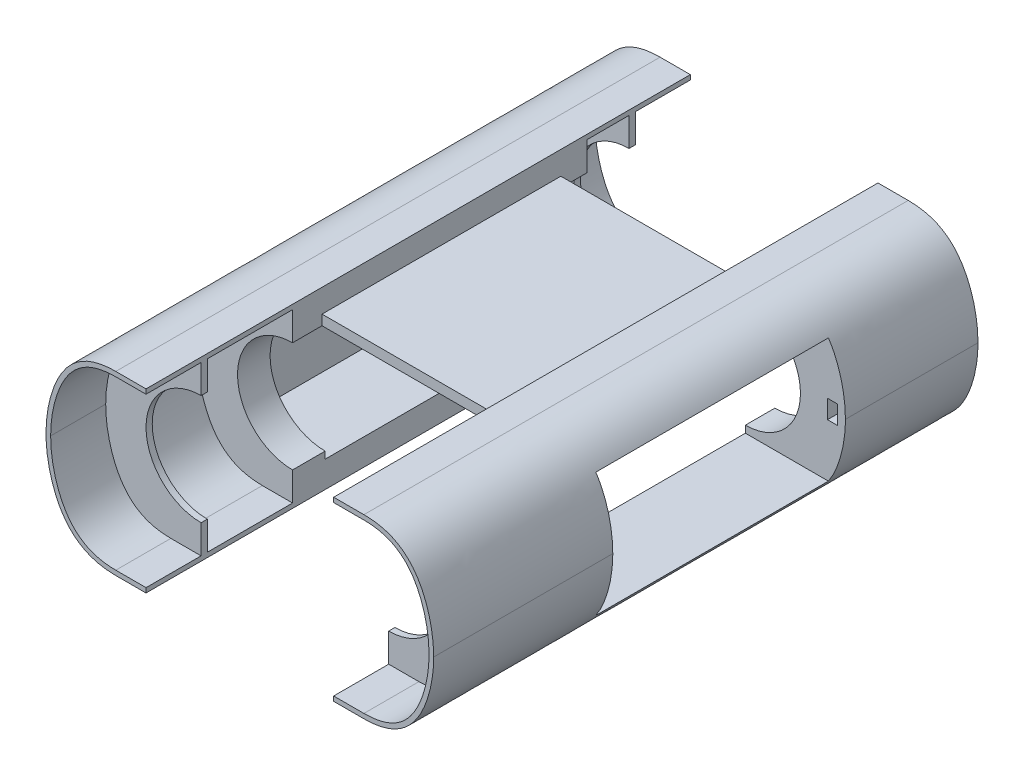
SolidWorks part; units mm, degrees
ref_plane "前视基准面" through (0, 0, 0) normal (0, 0, 1) x (1, 0, 0)
ref_plane "上视基准面" through (0, 0, 0) normal (0, 1, 0) x (1, 0, 0)
ref_plane "右视基准面" through (0, 0, 0) normal (1, 0, 0) x (0, 0, -1)
sketch "草图2" plane through (0, 0, 0) normal (0, 0, 1) x (1, 0, 0)
  line L3 (60.5, 57) -> (80, 57)
  line L4 (80, -57) -> (60.5, -57)
  line L6 (0, 0) -> (125, 0) construction
  line L7 (80, 57) -> (110.7152, 57) construction
  line L8 (110.7152, 57) -> (118.0231, 36.993) construction
  line L9 (118.0231, 36.993) -> (125, 20.498) construction
  line L10 (125, 20.498) -> (125, 0) construction
  line L11 (80, -57) -> (110.7152, -57) construction
  line L17 (110.7152, -57) -> (118.0231, -36.993) construction
  line L18 (118.0231, -36.993) -> (125, -20.498) construction
  line L19 (125, -20.498) -> (125, 0) construction
  line L20 (60.5, 57) -> (60.5, 35.5)
  line L21 (60.5, -35.5) -> (60.5, -57)
  circle A2 centre (60.5, 0) radius 48 construction
  arc A3 (60.5, -35.5) -> (60.5, 35.5) centre (60.5, 0) ccw
  spline S0 degree 4 poles (80, 57) (110.7152, 57) (118.0231, 36.993) (125, 20.498) (125, 0) knots 0 0 0 0 0 1 1 1 1 1
  spline S1 degree 4 poles (80, -57) (110.7152, -57) (118.0231, -36.993) (125, -20.498) (125, 0) knots 0 0 0 0 0 1 1 1 1 1
  dimension "D1" = 96
  dimension "D5" = 71
  dimension "D3" = 125
  dimension "D4" = 114
extrude "凸台-拉伸1" add sketch "草图2" against normal blind 140 and the other way blind 140
sketch "草图5" plane through (0, 0, 140) normal (0, 0, 1) x (1, 0, 0)
  line L4 (60.5, -35.5) -> (60.5, -57)
  line L5 (60.5, -57) -> (80, -57)
  line L6 (80, 57) -> (60.5, 57)
  line L7 (60.5, 57) -> (60.5, 35.5)
  line L8 (60.5, -50) -> (60.5, -57)
  line L9 (60.5, -57) -> (80, -57)
  line L10 (80, 57) -> (60.5, 57)
  line L11 (60.5, 57) -> (60.5, 50)
  arc A0 (60.5, -50) -> (60.5, 50) centre (60.5, 0) ccw
  arc A1 (60.5, -35.5) -> (60.5, 35.5) centre (60.5, 0) ccw
  spline S2 degree 4 poles (-2185.0858, 1904.0706) (2039.0492, -2126.1178) (-1683.6914, 1923.0509) (1994.951, -1870.167) (-1888.5824, 2222.1027) knots -2.085011 -2.085011 -2.085011 -2.085011 -2.085011 3.566088 3.566088 3.566088 3.566088 3.566088 only from (80, -57) to (125, 0)
  spline S3 degree 4 poles (-1888.5421, -2222.0603) (1994.9281, 1870.1435) (-1683.6829, -1923.041) (2039.0546, 2126.1251) (-2185.1106, -1904.0942) knots -2.566073 -2.566073 -2.566073 -2.566073 -2.566073 3.085019 3.085019 3.085019 3.085019 3.085019 only from (125, 0) to (80, 57)
  spline S4 degree 4 poles (80, -57) (110.7152, -57) (118.0231, -36.993) (125, -20.498) (125, 0) knots 0 0 0 0 0 1 1 1 1 1
  spline S5 degree 4 poles (125, 0) (125, 20.498) (118.0231, 36.993) (110.7152, 57) (80, 57) knots 0 0 0 0 0 1 1 1 1 1
  dimension "D2" = 100
  dimension "D1" = 0
extrude "凸台-拉伸3" add sketch "草图5" along normal blind 35.5
mirror "镜向2" about plane through (0, 0, 0) normal (0, 0, 1) of "凸台-拉伸3"
sketch "草图6" plane through (60.5, 0, 0) normal (-1, 0, 0) x (0, 0, 1)
  line L0 (-90, 40) -> (-90, -40)
  line L1 (-90, -40) -> (60, -40)
  line L2 (60, -40) -> (60, 40)
  line L3 (60, 40) -> (-90, 40)
  line L4 (-140, 50) -> (-140, -50) construction
  dimension "D1" = 50
  dimension "D2" = 150
  dimension "D3" = 80
  dimension "D4" = 40
extrude "切除-拉伸2" cut sketch "草图6" against normal up to next
sketch "草图7" plane through (0, 0, -90) normal (0, 0, 1) x (1, 0, 0)
  line L0 (113.43, 6) -> (113.43, -6)
  line L1 (60.5, 57) -> (60.5, 50) construction
  line L2 (113.43, 6) -> (119.93, 6)
  line L3 (119.93, 6) -> (119.93, -6)
  line L4 (119.93, -6) -> (113.43, -6)
  dimension "D1" = 52.93
  dimension "D2" = 6.5
  dimension "D3" = 6
  dimension "D4" = 12
sketch "草图9" plane through (0, 0, 0) normal (0, 1, 0) x (1, 0, 0)
  line L0 (119.9292, -54.7428) -> (119.9292, -60) construction
  line L1 (113.4292, -39.7428) -> (119.9292, -39.7428) construction
  line L2 (119.9292, -39.7428) -> (119.9292, -54.7428) construction
  line L3 (119.9292, -54.7428) -> (116.9292, -54.7428) construction
  line L4 (125, -60) -> (114.0344, -60) construction
  line L5 (113.4292, -60) -> (119.9292, -60)
  line L6 (119.9292, -60) -> (119.9292, -75)
  line L7 (118.4292, -39.7428) -> (113.4292, -39.7428)
  line L8 (118.4292, -47.284) -> (118.4292, -39.7428)
  line L9 (118.4292, -54.7428) -> (118.4292, -47.284)
  line L10 (116.9292, -54.7428) -> (118.4292, -54.7428)
  line L11 (111.9292, -48.784) -> (116.9292, -54.7428)
  line L12 (113.4292, -47.284) -> (111.9292, -48.784)
  line L13 (113.4292, -39.7428) -> (113.4292, -47.284)
  line L14 (118.4292, -39.7428) -> (113.4292, -39.7428) construction
  line L17 (116.9292, -54.7428) -> (118.4292, -54.7428) construction
  line L18 (111.9292, -48.784) -> (116.9292, -54.7428) construction
  line L19 (113.4292, -47.284) -> (111.9292, -48.784) construction
  line L20 (113.4292, -39.7428) -> (113.4292, -47.284) construction
  line L21 (119.9292, -75) -> (116.9292, -75)
  line L22 (118.4292, -60) -> (113.4292, -60) construction
  line L23 (116.9292, -75) -> (118.4292, -75) construction
  line L24 (111.9292, -69.0412) -> (116.9292, -75)
  line L25 (113.4292, -67.5412) -> (111.9292, -69.0412)
  line L26 (113.4292, -60) -> (113.4292, -67.5412)
  dimension "D2" = 6.5
  dimension "D1" = 0
extrude "切除-拉伸4" cut sketch "草图9" against normal blind 6 and the other way blind 6
ref_plane "基准面1" through (0, 0, -15) normal (0, 0, -1) x (-1, 0, 0)
mirror "镜向3" about plane through (0, 0, -15) normal (0, 0, -1) of "切除-拉伸4"
sketch "草图10" plane through (60.5, 0, 0) normal (-1, 0, 0) x (0, 0, 1)
  line L0 (-90, 40) -> (-90, 35.5) construction
  line L1 (-90, 40) -> (-90, 35.5)
  line L2 (60, 40) -> (-90, 40) construction
  line L3 (60, 40) -> (-90, 40)
  line L4 (60, 35.5) -> (60, 40) construction
  line L5 (60, 35.5) -> (60, 40)
  line L6 (62, 35.5) -> (62, 42)
  line L7 (62, 42) -> (-92, 42)
  line L8 (-92, 42) -> (-92, 35.5)
  line L9 (-90, 35.5) -> (-92, 35.5)
  line L10 (62, 35.5) -> (60, 35.5)
  dimension "D1" = 2
extrude "凸台-拉伸4" add sketch "草图10" along normal blind 60.5
sketch "草图18" plane through (0, 0, 140) normal (0, 0, 1) x (1, 0, 0)
  line L14 (60.5, 54) -> (60.5, 35.5)
  line L15 (60.5, -35.5) -> (60.5, -54)
  line L16 (60.5, -54) -> (80, -54)
  line L17 (80, 54) -> (60.5, 54)
  line L18 (60.5, -54) -> (80, -54)
  line L19 (80, 54) -> (60.5, 54)
  arc A6 (60.5, -35.5) -> (60.5, 35.5) centre (60.5, 0) ccw construction
  arc A7 (60.5, -35.5) -> (60.5, 35.5) centre (60.5, 0) ccw
  spline S6 degree 3 poles (-2284.8174, 1786.782) (-267.8158, 65.4032) (22.7897, -72.0343) (94.2935, -51.9146) (95.9213, -51.3146) (98.9407, -49.9446) (100.3325, -49.1745) (102.9215, -47.4892) (104.1189, -46.5739) (106.3517, -44.6176) (107.387, -43.5765) (110.2859, -40.2914) (111.9438, -37.8856) (114.8342, -32.7781) (116.0659, -30.0773) (118.1749, -24.4868) (119.0523, -21.5978) (120.4814, -15.6836) (121.0332, -12.6589) (134.3799, 96.2922) (-53.4095, 288.2581) (-1857.1893, 2252.5098) knots -2.337511 -2.337511 -2.337511 -2.337511 0.125 0.125 0.1875 0.1875 0.25 0.25 0.3125 0.3125 0.375 0.375 0.5 0.5 0.625 0.625 0.75 0.75 0.875 0.875 5.144901 5.144901 5.144901 5.144901 only from (80, -54) to (122, 0)
  spline S7 degree 3 poles (-1857.2007, -2252.5222) (-53.4103, -288.2589) (134.3799, -96.2924) (121.0332, 12.6589) (120.4814, 15.6836) (119.0523, 21.5978) (118.1749, 24.4868) (116.0659, 30.0773) (114.8342, 32.7781) (111.9438, 37.8856) (110.2859, 40.2914) (107.387, 43.5765) (106.3517, 44.6176) (104.1189, 46.5739) (102.9215, 47.4892) (100.3325, 49.1745) (98.9407, 49.9446) (95.9213, 51.3146) (94.2935, 51.9146) (22.7905, 72.0341) (-267.8099, -65.4004) (-2284.7558, -1786.7295) knots -4.14491 -4.14491 -4.14491 -4.14491 0.125 0.125 0.25 0.25 0.375 0.375 0.5 0.5 0.625 0.625 0.6875 0.6875 0.75 0.75 0.8125 0.8125 0.875 0.875 3.337486 3.337486 3.337486 3.337486 only from (122, 0) to (80, 54)
  spline S8 degree 3 poles (80, -54) (84.8749, -54) (88.9838, -53.4087) (94.2935, -51.9146) (95.9213, -51.3146) (98.9407, -49.9446) (100.3325, -49.1745) (102.9215, -47.4892) (104.1189, -46.5739) (106.3517, -44.6176) (107.387, -43.5765) (110.2859, -40.2914) (111.9438, -37.8856) (114.8342, -32.7781) (116.0659, -30.0773) (118.1749, -24.4868) (119.0523, -21.5978) (120.4814, -15.6836) (121.0332, -12.6589) (121.7924, -6.4613) (122, -3.2887) (122, 0) knots 0 0 0 0 0.125 0.125 0.1875 0.1875 0.25 0.25 0.3125 0.3125 0.375 0.375 0.5 0.5 0.625 0.625 0.75 0.75 0.875 0.875 1 1 1 1
  spline S9 degree 3 poles (122, 0) (122, 3.2887) (121.7924, 6.4613) (121.0332, 12.6589) (120.4814, 15.6836) (119.0523, 21.5978) (118.1749, 24.4868) (116.0659, 30.0773) (114.8342, 32.7781) (111.9438, 37.8856) (110.2859, 40.2914) (107.387, 43.5765) (106.3517, 44.6176) (104.1189, 46.5739) (102.9215, 47.4892) (100.3325, 49.1745) (98.9407, 49.9446) (95.9213, 51.3146) (94.2935, 51.9146) (88.9838, 53.4087) (84.8749, 54) (80, 54) knots 0 0 0 0 0.125 0.125 0.25 0.25 0.375 0.375 0.5 0.5 0.625 0.625 0.6875 0.6875 0.75 0.75 0.8125 0.8125 0.875 0.875 1 1 1 1
  dimension "D1" = 3
extrude "切除-拉伸6" cut sketch "草图18" against normal blind 55 from offset 4 offset against normal yes
sketch "草图19" plane through (0, 0, -140) normal (0, 0, -1) x (-1, 0, 0)
  line L2 (-60.5, 54) -> (-60.5, 35.5)
  line L3 (-60.5, -35.5) -> (-60.5, -54)
  line L4 (-60.5, -54) -> (-80, -54)
  line L5 (-80, 54) -> (-60.5, 54)
  line L6 (-60.5, -54) -> (-80, -54)
  line L7 (-80, 54) -> (-60.5, 54)
  arc A0 (-60.5, 35.5) -> (-60.5, -35.5) centre (-60.5, 0) ccw construction
  arc A1 (-60.5, 35.5) -> (-60.5, -35.5) centre (-60.5, 0) ccw
  spline S4 degree 3 poles (2284.8174, 1786.782) (267.8158, 65.4032) (-22.7897, -72.0343) (-94.2935, -51.9146) (-95.9213, -51.3146) (-98.9407, -49.9446) (-100.3325, -49.1745) (-102.9215, -47.4892) (-104.1189, -46.5739) (-106.3517, -44.6176) (-107.387, -43.5765) (-110.2859, -40.2914) (-111.9438, -37.8856) (-114.8342, -32.7781) (-116.0659, -30.0773) (-118.1749, -24.4868) (-119.0523, -21.5978) (-120.4814, -15.6836) (-121.0332, -12.6589) (-134.3799, 96.2922) (53.4095, 288.2581) (1857.1893, 2252.5098) knots -2.337511 -2.337511 -2.337511 -2.337511 0.125 0.125 0.1875 0.1875 0.25 0.25 0.3125 0.3125 0.375 0.375 0.5 0.5 0.625 0.625 0.75 0.75 0.875 0.875 5.144901 5.144901 5.144901 5.144901 only from (-80, -54) to (-122, 0)
  spline S5 degree 3 poles (1857.2007, -2252.5222) (53.4103, -288.2589) (-134.3799, -96.2924) (-121.0332, 12.6589) (-120.4814, 15.6836) (-119.0523, 21.5978) (-118.1749, 24.4868) (-116.0659, 30.0773) (-114.8342, 32.7781) (-111.9438, 37.8856) (-110.2859, 40.2914) (-107.387, 43.5765) (-106.3517, 44.6176) (-104.1189, 46.5739) (-102.9215, 47.4892) (-100.3325, 49.1745) (-98.9407, 49.9446) (-95.9213, 51.3146) (-94.2935, 51.9146) (-22.7905, 72.0341) (267.8099, -65.4004) (2284.7558, -1786.7295) knots -4.14491 -4.14491 -4.14491 -4.14491 0.125 0.125 0.25 0.25 0.375 0.375 0.5 0.5 0.625 0.625 0.6875 0.6875 0.75 0.75 0.8125 0.8125 0.875 0.875 3.337486 3.337486 3.337486 3.337486 only from (-122, 0) to (-80, 54)
  spline S6 degree 3 poles (-80, -54) (-84.8749, -54) (-88.9838, -53.4087) (-94.2935, -51.9146) (-95.9213, -51.3146) (-98.9407, -49.9446) (-100.3325, -49.1745) (-102.9215, -47.4892) (-104.1189, -46.5739) (-106.3517, -44.6176) (-107.387, -43.5765) (-110.2859, -40.2914) (-111.9438, -37.8856) (-114.8342, -32.7781) (-116.0659, -30.0773) (-118.1749, -24.4868) (-119.0523, -21.5978) (-120.4814, -15.6836) (-121.0332, -12.6589) (-121.7924, -6.4613) (-122, -3.2887) (-122, 0) knots 0 0 0 0 0.125 0.125 0.1875 0.1875 0.25 0.25 0.3125 0.3125 0.375 0.375 0.5 0.5 0.625 0.625 0.75 0.75 0.875 0.875 1 1 1 1
  spline S7 degree 3 poles (-122, 0) (-122, 3.2887) (-121.7924, 6.4613) (-121.0332, 12.6589) (-120.4814, 15.6836) (-119.0523, 21.5978) (-118.1749, 24.4868) (-116.0659, 30.0773) (-114.8342, 32.7781) (-111.9438, 37.8856) (-110.2859, 40.2914) (-107.387, 43.5765) (-106.3517, 44.6176) (-104.1189, 46.5739) (-102.9215, 47.4892) (-100.3325, 49.1745) (-98.9407, 49.9446) (-95.9213, 51.3146) (-94.2935, 51.9146) (-88.9838, 53.4087) (-84.8749, 54) (-80, 54) knots 0 0 0 0 0.125 0.125 0.25 0.25 0.375 0.375 0.5 0.5 0.625 0.625 0.6875 0.6875 0.75 0.75 0.8125 0.8125 0.875 0.875 1 1 1 1
  dimension "D1" = 3
extrude "切除-拉伸7" cut sketch "草图19" against normal blind 27 from offset 4 offset against normal yes
sketch "草图20" plane through (0, 0, 175.5) normal (0, 0, 1) x (1, 0, 0)
  line L2 (60.5, 54) -> (60.5, 50)
  line L3 (60.5, -50) -> (60.5, -54)
  line L4 (60.5, -54) -> (80, -54)
  line L5 (80, 54) -> (60.5, 54)
  line L6 (60.5, -54) -> (80, -54)
  line L7 (80, 54) -> (60.5, 54)
  arc A0 (60.5, -50) -> (60.5, 50) centre (60.5, 0) ccw construction
  arc A1 (60.5, -50) -> (60.5, 50) centre (60.5, 0) ccw
  spline S4 degree 3 poles (-2284.8174, 1786.782) (-267.8158, 65.4032) (22.7897, -72.0343) (94.2935, -51.9146) (95.9213, -51.3146) (98.9407, -49.9446) (100.3325, -49.1745) (102.9215, -47.4892) (104.1189, -46.5739) (106.3517, -44.6176) (107.387, -43.5765) (110.2859, -40.2914) (111.9438, -37.8856) (114.8342, -32.7781) (116.0659, -30.0773) (118.1749, -24.4868) (119.0523, -21.5978) (120.4814, -15.6836) (121.0332, -12.6589) (134.3799, 96.2922) (-53.4095, 288.2581) (-1857.1893, 2252.5098) knots -2.337511 -2.337511 -2.337511 -2.337511 0.125 0.125 0.1875 0.1875 0.25 0.25 0.3125 0.3125 0.375 0.375 0.5 0.5 0.625 0.625 0.75 0.75 0.875 0.875 5.144901 5.144901 5.144901 5.144901 only from (80, -54) to (122, 0)
  spline S5 degree 3 poles (-1857.2007, -2252.5222) (-53.4103, -288.2589) (134.3799, -96.2924) (121.0332, 12.6589) (120.4814, 15.6836) (119.0523, 21.5978) (118.1749, 24.4868) (116.0659, 30.0773) (114.8342, 32.7781) (111.9438, 37.8856) (110.2859, 40.2914) (107.387, 43.5765) (106.3517, 44.6176) (104.1189, 46.5739) (102.9215, 47.4892) (100.3325, 49.1745) (98.9407, 49.9446) (95.9213, 51.3146) (94.2935, 51.9146) (22.7905, 72.0341) (-267.8099, -65.4004) (-2284.7558, -1786.7295) knots -4.14491 -4.14491 -4.14491 -4.14491 0.125 0.125 0.25 0.25 0.375 0.375 0.5 0.5 0.625 0.625 0.6875 0.6875 0.75 0.75 0.8125 0.8125 0.875 0.875 3.337486 3.337486 3.337486 3.337486 only from (122, 0) to (80, 54)
  spline S6 degree 3 poles (80, -54) (84.8749, -54) (88.9838, -53.4087) (94.2935, -51.9146) (95.9213, -51.3146) (98.9407, -49.9446) (100.3325, -49.1745) (102.9215, -47.4892) (104.1189, -46.5739) (106.3517, -44.6176) (107.387, -43.5765) (110.2859, -40.2914) (111.9438, -37.8856) (114.8342, -32.7781) (116.0659, -30.0773) (118.1749, -24.4868) (119.0523, -21.5978) (120.4814, -15.6836) (121.0332, -12.6589) (121.7924, -6.4613) (122, -3.2887) (122, 0) knots 0 0 0 0 0.125 0.125 0.1875 0.1875 0.25 0.25 0.3125 0.3125 0.375 0.375 0.5 0.5 0.625 0.625 0.75 0.75 0.875 0.875 1 1 1 1
  spline S7 degree 3 poles (122, 0) (122, 3.2887) (121.7924, 6.4613) (121.0332, 12.6589) (120.4814, 15.6836) (119.0523, 21.5978) (118.1749, 24.4868) (116.0659, 30.0773) (114.8342, 32.7781) (111.9438, 37.8856) (110.2859, 40.2914) (107.387, 43.5765) (106.3517, 44.6176) (104.1189, 46.5739) (102.9215, 47.4892) (100.3325, 49.1745) (98.9407, 49.9446) (95.9213, 51.3146) (94.2935, 51.9146) (88.9838, 53.4087) (84.8749, 54) (80, 54) knots 0 0 0 0 0.125 0.125 0.25 0.25 0.375 0.375 0.5 0.5 0.625 0.625 0.6875 0.6875 0.75 0.75 0.8125 0.8125 0.875 0.875 1 1 1 1
  dimension "D1" = 3
extrude "切除-拉伸8" cut sketch "草图20" against normal up to surface (35.5 mm away) up to face at (81.875, 0, 140)
sketch "草图21" plane through (0, 0, -175.5) normal (0, 0, -1) x (-1, 0, 0)
  line L2 (-60.5, -50) -> (-60.5, -54)
  line L3 (-60.5, 54) -> (-60.5, 50)
  line L4 (-60.5, -54) -> (-80, -54)
  line L5 (-80, 54) -> (-60.5, 54)
  line L6 (-60.5, -54) -> (-80, -54)
  line L7 (-80, 54) -> (-60.5, 54)
  arc A0 (-60.5, 50) -> (-60.5, -50) centre (-60.5, 0) ccw construction
  arc A1 (-60.5, 50) -> (-60.5, -50) centre (-60.5, 0) ccw
  spline S4 degree 3 poles (2284.8174, 1786.782) (267.8158, 65.4032) (-22.7897, -72.0343) (-94.2935, -51.9146) (-95.9213, -51.3146) (-98.9407, -49.9446) (-100.3325, -49.1745) (-102.9215, -47.4892) (-104.1189, -46.5739) (-106.3517, -44.6176) (-107.387, -43.5765) (-110.2859, -40.2914) (-111.9438, -37.8856) (-114.8342, -32.7781) (-116.0659, -30.0773) (-118.1749, -24.4868) (-119.0523, -21.5978) (-120.4814, -15.6836) (-121.0332, -12.6589) (-134.3799, 96.2922) (53.4095, 288.2581) (1857.1893, 2252.5098) knots -2.337511 -2.337511 -2.337511 -2.337511 0.125 0.125 0.1875 0.1875 0.25 0.25 0.3125 0.3125 0.375 0.375 0.5 0.5 0.625 0.625 0.75 0.75 0.875 0.875 5.144901 5.144901 5.144901 5.144901 only from (-80, -54) to (-122, 0)
  spline S5 degree 3 poles (1857.2007, -2252.5222) (53.4103, -288.2589) (-134.3799, -96.2924) (-121.0332, 12.6589) (-120.4814, 15.6836) (-119.0523, 21.5978) (-118.1749, 24.4868) (-116.0659, 30.0773) (-114.8342, 32.7781) (-111.9438, 37.8856) (-110.2859, 40.2914) (-107.387, 43.5765) (-106.3517, 44.6176) (-104.1189, 46.5739) (-102.9215, 47.4892) (-100.3325, 49.1745) (-98.9407, 49.9446) (-95.9213, 51.3146) (-94.2935, 51.9146) (-22.7905, 72.0341) (267.8099, -65.4004) (2284.7558, -1786.7295) knots -4.14491 -4.14491 -4.14491 -4.14491 0.125 0.125 0.25 0.25 0.375 0.375 0.5 0.5 0.625 0.625 0.6875 0.6875 0.75 0.75 0.8125 0.8125 0.875 0.875 3.337486 3.337486 3.337486 3.337486 only from (-122, 0) to (-80, 54)
  spline S6 degree 3 poles (-80, -54) (-84.8749, -54) (-88.9838, -53.4087) (-94.2935, -51.9146) (-95.9213, -51.3146) (-98.9407, -49.9446) (-100.3325, -49.1745) (-102.9215, -47.4892) (-104.1189, -46.5739) (-106.3517, -44.6176) (-107.387, -43.5765) (-110.2859, -40.2914) (-111.9438, -37.8856) (-114.8342, -32.7781) (-116.0659, -30.0773) (-118.1749, -24.4868) (-119.0523, -21.5978) (-120.4814, -15.6836) (-121.0332, -12.6589) (-121.7924, -6.4613) (-122, -3.2887) (-122, 0) knots 0 0 0 0 0.125 0.125 0.1875 0.1875 0.25 0.25 0.3125 0.3125 0.375 0.375 0.5 0.5 0.625 0.625 0.75 0.75 0.875 0.875 1 1 1 1
  spline S7 degree 3 poles (-122, 0) (-122, 3.2887) (-121.7924, 6.4613) (-121.0332, 12.6589) (-120.4814, 15.6836) (-119.0523, 21.5978) (-118.1749, 24.4868) (-116.0659, 30.0773) (-114.8342, 32.7781) (-111.9438, 37.8856) (-110.2859, 40.2914) (-107.387, 43.5765) (-106.3517, 44.6176) (-104.1189, 46.5739) (-102.9215, 47.4892) (-100.3325, 49.1745) (-98.9407, 49.9446) (-95.9213, 51.3146) (-94.2935, 51.9146) (-88.9838, 53.4087) (-84.8749, 54) (-80, 54) knots 0 0 0 0 0.125 0.125 0.25 0.25 0.375 0.375 0.5 0.5 0.625 0.625 0.6875 0.6875 0.75 0.75 0.8125 0.8125 0.875 0.875 1 1 1 1
  dimension "D1" = 3
extrude "切除-拉伸9" cut sketch "草图21" against normal up to surface (35.5 mm away) up to face at (81.875, 0, -140)
mirror "镜向9" about plane through (0, 0, 0) normal (-1, 0, 0) of bodies 117
sketch "草图23" plane through (0, 0, -90) normal (0, 0, 1) x (1, 0, 0)
  line L0 (-114.0344, 40) -> (-110, 40)
  line L1 (-110, 40) -> (-110, -40)
  line L2 (-114.0344, -40) -> (-60.5, -40) construction
  line L3 (-110, -40) -> (-114.0344, -40)
  spline S0 degree 4 poles (1445.3353, 1205.2622) (-1368.1044, -1419.777) (1038.0249, 1237.6) (-1340.3199, -1192.9417) (1200.8488, 1496.1002) knots -1.799466 -1.799466 -1.799466 -1.799466 -1.799466 3.275004 3.275004 3.275004 3.275004 3.275004 only from (-114.0344, -40) to (-125, 0) construction
  spline S1 degree 4 poles (1200.8981, -1496.1524) (-1340.3558, 1192.9785) (1038.0508, -1237.6284) (-1368.122, 1419.7941) (1445.3415, -1205.2679) knots -2.275029 -2.275029 -2.275029 -2.275029 -2.275029 2.799468 2.799468 2.799468 2.799468 2.799468 only from (-125, 0) to (-114.0344, 40) construction
  spline S2 degree 4 poles (-114.0344, -40) (-119.7719, -31.4467) (-122.8884, -21.3418) (-125, -11.2767) (-125, 0) knots 0.449865 0.449865 0.449865 0.449865 0.449865 1 1 1 1 1
  spline S3 degree 4 poles (-125, 0) (-125, 11.2767) (-122.8884, 21.3418) (-119.7719, 31.4467) (-114.0344, 40) knots 0 0 0 0 0 0.550135 0.550135 0.550135 0.550135 0.550135
  dimension "D1" = 110
extrude "凸台-拉伸5" add sketch "草图23" along normal up to next
